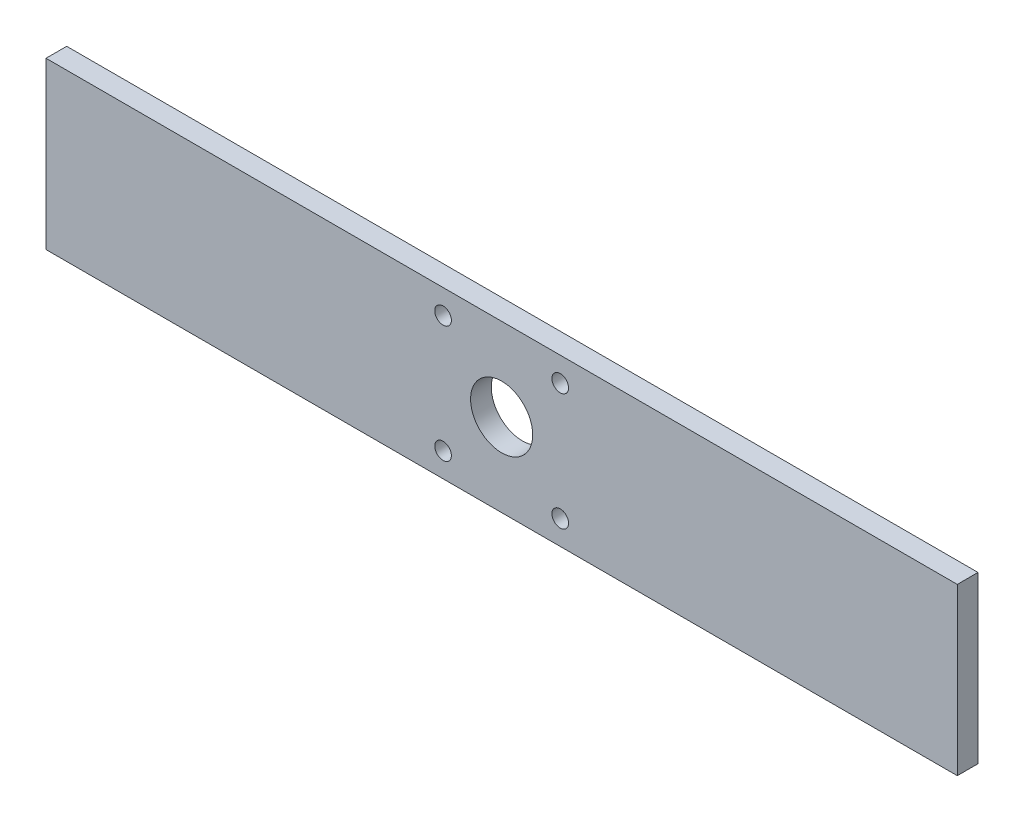
SolidWorks part; units mm, degrees
ref_plane "Front Plane" through (0, 0, 0) normal (0, 0, 1) x (1, 0, 0)
ref_plane "Top Plane" through (0, 0, 0) normal (0, 1, 0) x (1, 0, 0)
ref_plane "Right Plane" through (0, 0, 0) normal (1, 0, 0) x (0, 0, -1)
sketch "Sketch1" plane through (0, 0, 0) normal (0, 0, 1) x (1, 0, 0)
  line L1 (-139.7, -25.4) -> (139.7, -25.4)
  line L2 (-139.7, -25.4) -> (-139.7, 25.4)
  line L3 (-139.7, 25.4) -> (139.7, 25.4)
  line L4 (139.7, -25.4) -> (139.7, 25.4)
  line L5 (-139.7, -25.4) -> (139.7, 25.4) construction
  line L6 (-139.7, 25.4) -> (139.7, -25.4) construction
  point P0 (0, 0)
  dimension "D1" = 279.4
  dimension "D2" = 50.8
extrude "Boss-Extrude1" add sketch "Sketch1" along normal blind 6.35
sketch "Sketch2" plane through (0, 0, 6.35) normal (0, 0, 1) x (1, 0, 0)
  circle A0 centre (0, 0) radius 9.525
  dimension "D1" = 19.05
extrude "Cut-Extrude1" cut sketch "Sketch2" against normal through all
hole_wizard "#7 (0.201) Diameter Hole1" positions "Sketch4" profile "Sketch3" hole size "#7" standard "Ansi Inch" end condition through all
sketch "Sketch4" plane through (0, 0, 6.35) normal (0, 0, 1) x (1, 0, 0)
  line L0 (17.9605, 17.9605) -> (0, 0) construction
  line L1 (0, 0) -> (9.525, 0) construction
  circle A0 centre (0, 0) radius 9.525 construction
  point P0 (17.9605, 17.9605)
  dimension "D1" = 25.4
  dimension "D2" = 45
sketch "Sketch3" plane through (17.9605, 17.9605, 6.35) normal (1, 0, 0) x (0, -1, 0)
  line L0 (0, 0) -> (0, 6.35)
  line L1 (0, 6.35) -> (2.5527, 6.35)
  line L2 (2.5527, 6.35) -> (2.5527, 0)
  line L5 (2.5527, 0) -> (0, 0)
  line L11 (0, -6.35) -> (0, 107.95) construction
  dimension "Thru Hole Dia." = 5.1054
  dimension "Thru Hole Depth" = 6.35
pattern_circular "CirPattern1" count 4 over 360 about axis through (0, 0, 0) along (0, 0, 1) of "#7 (0.201) Diameter Hole1"
